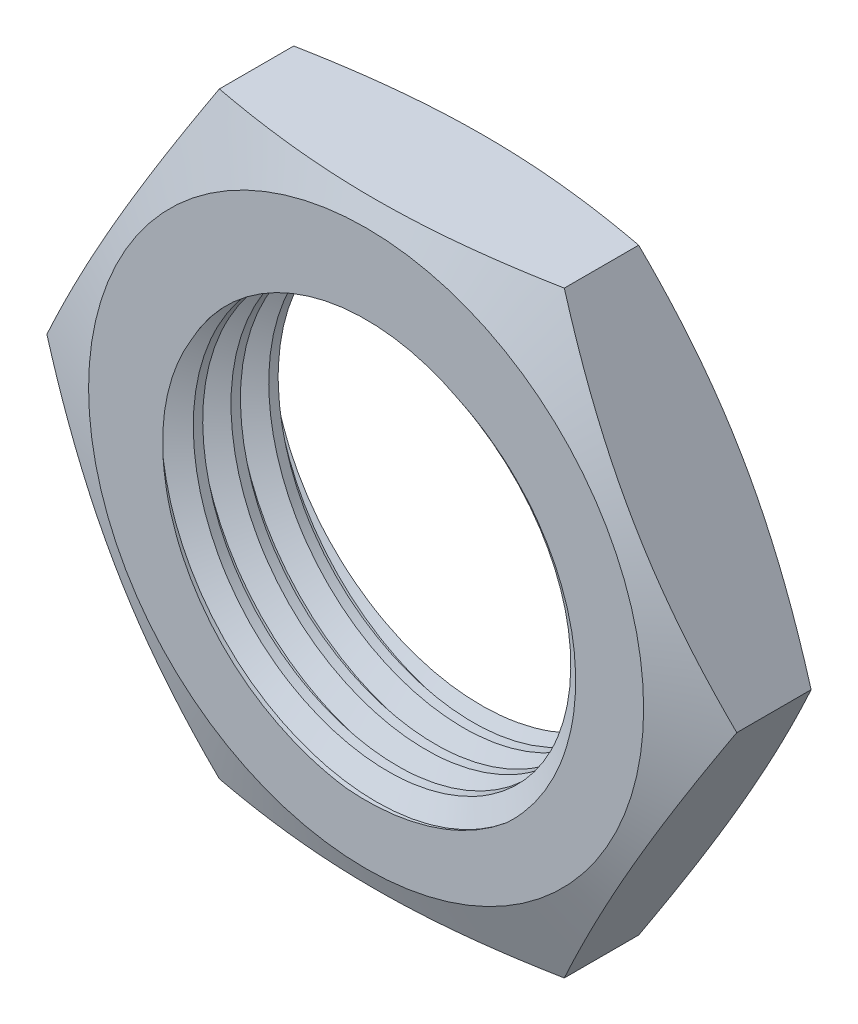
SolidWorks part; units mm, degrees
ref_plane "Front Plane" through (0, 0, 0) normal (0, 0, 1) x (1, 0, 0)
ref_plane "Top Plane" through (0, 0, 0) normal (0, 1, 0) x (1, 0, 0)
ref_plane "Right Plane" through (0, 0, 0) normal (1, 0, 0) x (0, 0, -1)
sketch "Sketch1" plane through (0, 0, 0) normal (0, 0, 1) x (1, 0, 0)
  line L1 (5.4848, 0) -> (2.7424, 4.75)
  line L2 (2.7424, 4.75) -> (-2.7424, 4.75)
  line L3 (-2.7424, 4.75) -> (-5.4848, 0)
  line L4 (-5.4848, 0) -> (-2.7424, -4.75)
  line L5 (-2.7424, -4.75) -> (2.7424, -4.75)
  line L6 (2.7424, -4.75) -> (5.4848, 0)
  circle A0 centre (0, 0) radius 4.75 construction
  circle A1 centre (0, 0) radius 3.15
  dimension "D1" = 9.5
  dimension "D2" = 6.3
extrude "Boss-Extrude1" add sketch "Sketch1" along normal blind 2
sketch "Sketch2" plane through (0, 0, 0) normal (1, 0, 0) x (0, 0, -1)
  line L4 (-1.218, 6.4633) -> (-1.218, 0) construction
  line L5 (-2, 0) -> (0, 0) construction
  line L6 (-1.218, 0) -> (-3.7171, 0) construction
  line L7 (-1.218, 6.4633) -> (-3.7171, 6.4633)
  line L9 (-1.218, 6.4633) -> (-2.7019, 2.5723)
  line L10 (-2.7019, 2.5723) -> (-3.7171, 2.5695)
  line L11 (-3.7171, 6.4633) -> (-3.7171, 2.5695)
  point P8 (0, 0)
  point P9 (-1.5418, 6.4633)
  point P10 (0, 0)
  point P11 (-1.218, 0)
revolve "Cut-Revolve4" cut sketch "Sketch2" angle 360 about L6
ref_plane "Plane1" through (0, 0, 1) normal (0, 0, -1) x (-1, 0, 0)
mirror "Mirror1" about plane through (0, 0, 1) normal (0, 0, -1) of "Cut-Revolve4"
thread "Thread1" pitch 0.6 method cut profile "Thread Profile1" start angle 2, offset 0.5, length 5, pitch 0.6, diameter 6.3
ref_plane "Plane2" through (3.1481, 0.1099, -0.5) normal (0.0349, -0.9994, 0) x (0.9994, 0.0349, 0)
sketch "Thread Profile1" plane through (3.1481, 0.1099, -0.5) normal (0.0349, -0.9994, 0) x (0.9994, 0.0349, 0)
  line L0 (0, 0) -> (0, 0.6) construction
  line L1 (0, 0) -> (0.3248, 0.1875)
  line L2 (0.3248, 0.1875) -> (0.3248, 0.2625)
  line L3 (0.3248, 0.2625) -> (0, 0.45)
  line L4 (0.3248, 0.225) -> (0, 0.225) construction
  line L11 (0, 0) -> (0, 0.45)
  point P2 (0, 0)
  dimension "Pitch" = 0.6
  dimension "Profile_Angle" = 60
  dimension "Profile_Land" = 0.075
  dimension "Profile_Height" = 0.3248
